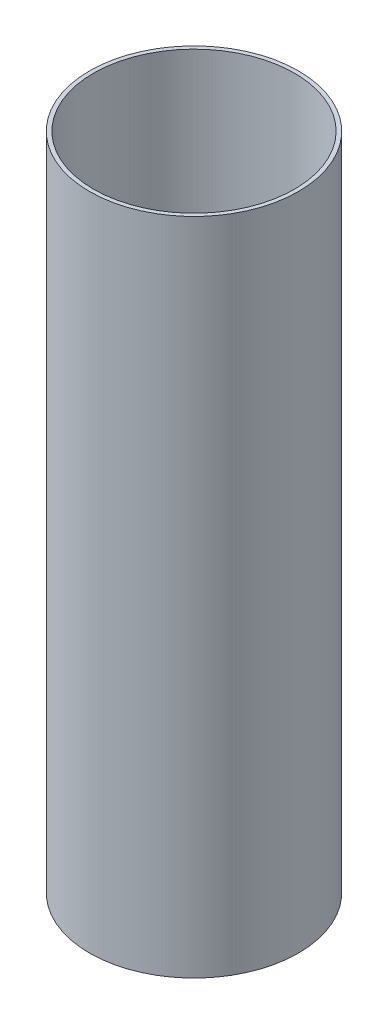
SolidWorks part; units mm, degrees
ref_plane "Front Plane" through (0, 0, 0) normal (0, 0, 1) x (1, 0, 0)
ref_plane "Top Plane" through (0, 0, 0) normal (0, 1, 0) x (1, 0, 0)
ref_plane "Right Plane" through (0, 0, 0) normal (1, 0, 0) x (0, 0, -1)
sketch "Sketch1" plane through (0, 0, 0) normal (0, 1, 0) x (1, 0, 0)
  circle A0 centre (0, 0) radius 38.1
  circle A1 centre (0, 0) radius 39.6
  dimension "D1" = 76.2
  dimension "D2" = 1.5
extrude "Boss-Extrude1" add sketch "Sketch1" along normal blind 250
